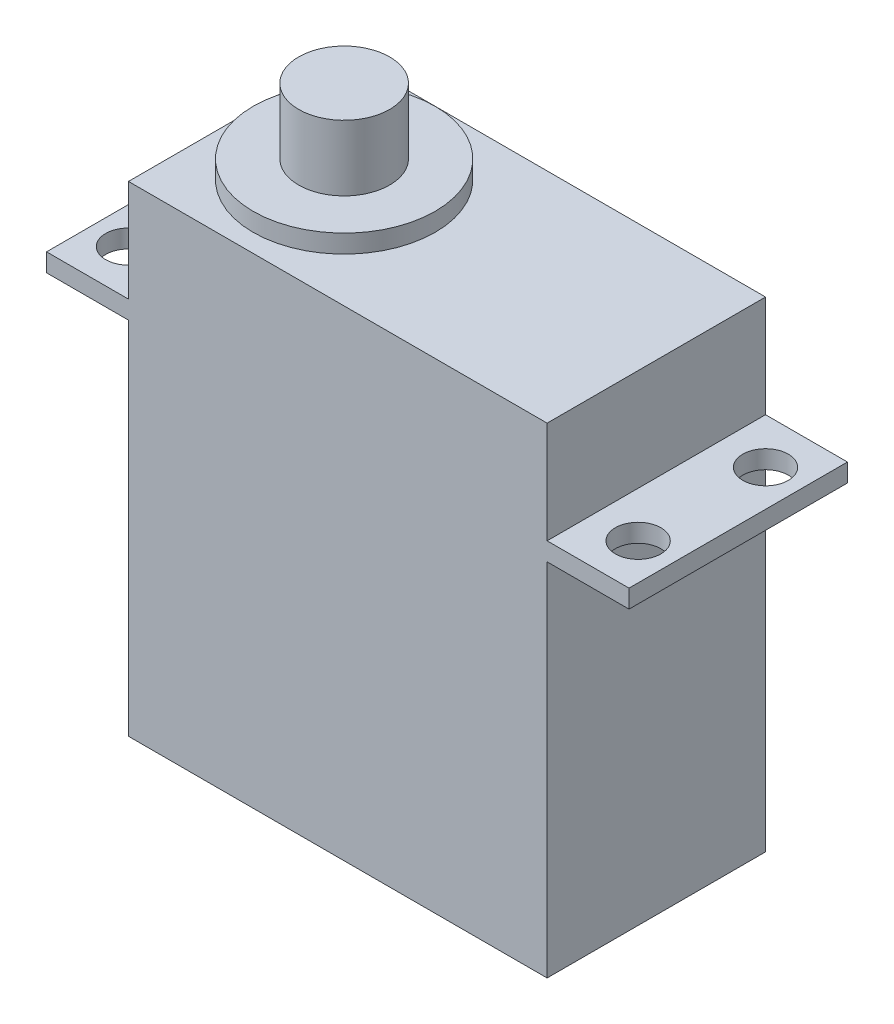
SolidWorks part; units mm, degrees
ref_plane "前视基准面" through (0, 0, 0) normal (0, 0, 1) x (1, 0, 0)
ref_plane "上视基准面" through (0, 0, 0) normal (0, 1, 0) x (1, 0, 0)
ref_plane "右视基准面" through (0, 0, 0) normal (1, 0, 0) x (0, 0, -1)
sketch "草图1" plane through (0, 0, 0) normal (0, 1, 0) x (1, 0, 0)
  line L0 (-33.3391, 0) -> (33.3391, 0) construction
  line L1 (0, 35.5304) -> (0, -35.5304) construction
  line L3 (-16, 6) -> (16, 6)
  line L4 (-16, 6) -> (-16, -6)
  line L5 (-16, -6) -> (16, -6)
  line L6 (16, 6) -> (16, -6)
  line L7 (-16, 6) -> (16, -6) construction
  line L8 (-16, -6) -> (16, 6) construction
  line L9 (11.5, -6) -> (-11.5, -6)
  line L10 (11.5, -6) -> (11.5, 6)
  line L11 (11.5, 6) -> (-11.5, 6)
  line L12 (-11.5, -6) -> (-11.5, 6)
  line L13 (11.5, -6) -> (-11.5, 6) construction
  line L14 (11.5, 6) -> (-11.5, -6) construction
  circle A0 centre (-14, 3.5) radius 1.25
  circle A1 centre (-14, -3.5) radius 1.25
  circle A2 centre (14, 3.5) radius 1.25
  circle A3 centre (14, -3.5) radius 1.25
  point P0 (0, 0)
  point P4 (0, 0)
  point P8 (0, 0)
  point P13 (0, 0)
  dimension "D4" = 2.5
  dimension "D1" = 12
  dimension "D2" = 32
  dimension "D3" = 23
  dimension "D5" = 28
  dimension "D6" = 7
extrude "凸台-拉伸1" add sketch "草图1" along normal blind 6.6 and the other way blind 19.8 contours L12 L5 L10 L3 region at (0, 0, 0)
extrude "凸台-拉伸2" add sketch "草图1<3>" along normal blind 1 contours L10 L5 L6 L3 A3 A2 | L5 L12 L3 L4 A1 A0 region at (-13.6944, 0, 0) region at (13.6944, 0, 0)
sketch "草图1<3>" plane through (0, 0, 0) normal (0, 1, 0) x (1, 0, 0) same geometry as "草图1"
sketch "草图2" plane through (0, 6.6, 0) normal (0, 1, 0) x (1, 0, 0)
  line L0 (-33.3391, 0) -> (33.3391, 0) construction
  line L1 (-11.5, -6) -> (-11.5, 6) construction
  circle A0 centre (-5.65, 0) radius 2.5
  dimension "D1" = 5
  dimension "D2" = 5.85
extrude "凸台-拉伸3" add sketch "草图2" along normal blind 4.6
sketch "草图3" plane through (0, 6.6, 0) normal (0, 1, 0) x (1, 0, 0)
  circle A0 centre (-5.65, 0) radius 5
  dimension "D1" = 10
extrude "凸台-拉伸4" add sketch "草图3" along normal blind 1
